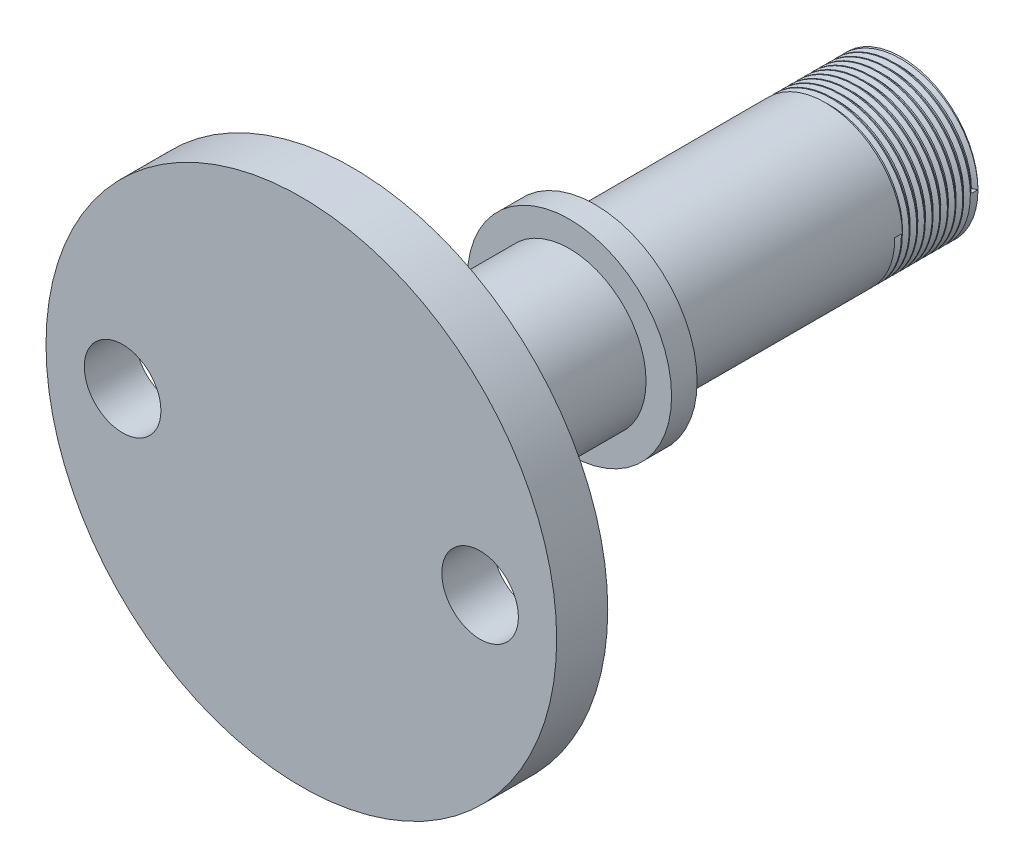
SolidWorks part; units mm, degrees
material "Cast Stainless Steel"
ref_plane "Front Plane" through (0, 0, 0) normal (0, 0, 1) x (1, 0, 0)
ref_plane "Top Plane" through (0, 0, 0) normal (0, 1, 0) x (1, 0, 0)
ref_plane "Right Plane" through (0, 0, 0) normal (1, 0, 0) x (0, 0, -1)
sketch "Sketch1" plane through (0, 0, 0) normal (0, 0, 1) x (1, 0, 0)
  circle A0 centre (0, 0) radius 3
  dimension "D1" = 6
extrude "Boss-Extrude1" add sketch "Sketch1" against normal mid plane 21.5
sketch "Sketch2" plane through (0, 0, 10.75) normal (0, 0, 1) x (1, 0, 0)
  circle A0 centre (0, 0) radius 10
  dimension "D1" = 20
extrude "Boss-Extrude2" add sketch "Sketch2" along normal blind 2
sketch "Sketch3" plane through (0, 0, 0) normal (0, 1, 0) x (1, 0, 0)
  line L0 (3, 10.75) -> (-3, 10.75) construction
  circle A0 centre (0, 9.25) radius 0.5
  dimension "D2" = 1
  dimension "D1" = 1.5
extrude "Cut-Extrude1" [suppressed] cut sketch "Sketch3" against normal through all both draft 1 and the other way through all draft outward yes
thread "Thread1" pitch 0.3 method cut profile "Thread Profile2" start angle 0, offset 0, length 0, pitch 0.3, diameter 6
ref_plane "Plane2" through (3, 0, -10.75) normal (0, -1, 0) x (1, 0, 0)
sketch "Thread Profile2" plane through (3, 0, -10.75) normal (0, -1, 0) x (1, 0, 0)
  line L0 (0, 0) -> (0, 0.3) construction
  line L11 (0, 0) -> (0, 0.2625)
  line L12 (0, 0.2625) -> (-0.1624, 0.1687)
  line L13 (-0.1624, 0.1687) -> (-0.1624, 0.0937)
  line L15 (-0.1624, 0.0937) -> (0, 0)
  line L17 (-0.1624, 0.1312) -> (0, 0.1312) construction
  point P2 (0, 0)
  dimension "Pitch" = 0.3
  dimension "Profile_Angle" = 60
  dimension "Profile_Land" = 0.075
  dimension "Profile_Height" = 0.1624
sketch "Sketch4" plane through (0, 0, 12.75) normal (0, 0, 1) x (1, 0, 0)
  circle A1 centre (7, 0) radius 1.5
  circle A3 centre (-7, 0) radius 1.5
  dimension "D3" = 3
  dimension "D4" = 3
  dimension "D1" = 7
  dimension "D2" = 7
extrude "Cut-Extrude2" cut sketch "Sketch4" against normal up to next
ref_plane "Plane3" through (0, 0, 2.25) normal (0, 0, -1) x (-1, 0, 0)
sketch "Sketch5" plane through (0, 0, 2.25) normal (0, 0, -1) x (-1, 0, 0)
  circle A0 centre (0, 0) radius 4
extrude "Boss-Extrude3" add sketch "Sketch5" along normal blind 1
